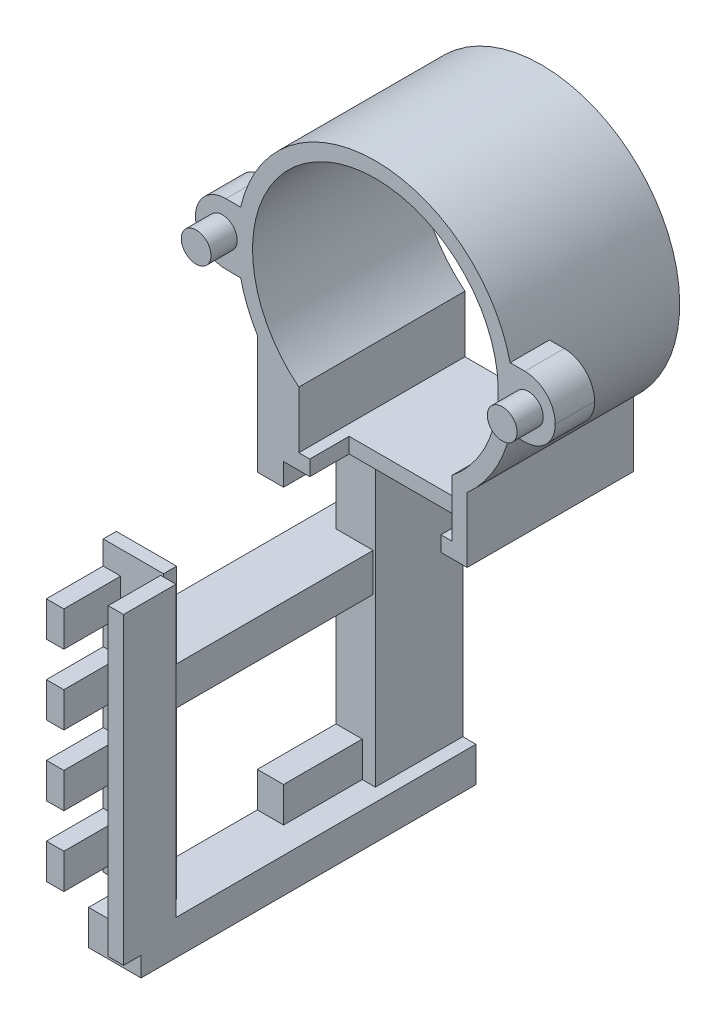
SolidWorks part; units mm, degrees
ref_plane "Plan de face" through (0, 0, 0) normal (0, 0, 1) x (1, 0, 0)
ref_plane "Plan de dessus" through (0, 0, 0) normal (0, 1, 0) x (1, 0, 0)
ref_plane "Plan de droite" through (0, 0, 0) normal (1, 0, 0) x (0, 0, -1)
sketch "Esquisse1" plane through (0, 0, 0) normal (0, 0, 1) x (1, 0, 0)
  line L0 (-10.5, -11.8064) -> (-10.5, -19.2427)
  line L2 (-8.75, -10.9927) -> (-8.75, -17.4927)
  line L3 (-8.75, -17.4927) -> (8.75, -17.4927)
  line L4 (8.75, -10.9927) -> (8.75, -17.4927)
  line L5 (-10.5, -19.2427) -> (10.5, -19.2427)
  line L6 (10.5, -11.8064) -> (10.5, -19.2427)
  arc A0 (8.75, -10.9927) -> (-8.75, -10.9927) centre (0, 0) ccw
  arc A1 (10.5, -11.8064) -> (-10.5, -11.8064) centre (0, 0) ccw
  dimension "D1" = 28.1
  dimension "D2" = 17.5
  dimension "D3" = 6.5
  dimension "D4" = 1.75
extrude "Boss.-Extru.1" add sketch "Esquisse1" along normal blind 19
sketch "Esquisse2" plane through (0, 0, 19) normal (0, 0, 1) x (1, 0, 0)
  line L0 (0, -19.2427) -> (0, 17.157) construction
  line L1 (-10.5, -19.2427) -> (10.5, -19.2427) construction
  line L2 (0, 0) -> (-25.7898, 0) construction
  line L3 (-15.4075, 3.5) -> (-17.0953, 3.5)
  line L4 (-15.4075, -3.5) -> (-17.0953, -3.5)
  line L5 (15.4075, -3.5) -> (17.0953, -3.5)
  line L6 (15.4075, 3.5) -> (17.0953, 3.5)
  circle A0 centre (-17.5, 0) radius 1.7
  arc A1 (10.5, -11.8064) -> (-10.5, -11.8064) centre (0, 0) ccw construction
  arc A2 (-17.0953, 3.5) -> (-20.5697, 0) centre (-17.0953, 0.0255) ccw
  arc A3 (-17.0953, -3.5) -> (-20.5697, 0) centre (-17.0953, -0.0255) cw
  circle A4 centre (17.5, 0) radius 1.7
  arc A5 (17.0953, -3.5) -> (20.5697, 0) centre (17.0953, -0.0255) ccw
  arc A6 (17.0953, 3.5) -> (20.5697, 0) centre (17.0953, 0.0255) cw
  arc A7 (-15.4075, -3.5) -> (-15.4075, 3.5) centre (0, 0) cw
  arc A8 (15.4075, -3.5) -> (15.4075, 3.5) centre (0, 0) ccw
  arc M1 (10.5, -11.8064) -> (-10.5, -11.8064) centre (0, 0) ccw
  dimension "D1" = 3.4
  dimension "D2" = 3.5
extrude "Boss.-Extru.8" add sketch "Esquisse2" against normal blind 4.5 separate body contours A3 L4 A0 L3 A2 M1 | A6 L6 A4 L5 A5 M1 | A0 | A4 region at (-17.5, 0, 19) region at (-15.788, 1.7707, 19) region at (17.5, 0, 19) region at (16.2514, 3.413, 19)
extrude "Boss.-Extru.9" add sketch "Esquisse2<4>" along normal blind 3 contours A0 | A4 region at (-17.5, 0, 19) region at (17.5, 0, 19)
sketch "Esquisse2<4>" plane through (0, 0, 19) normal (0, 0, 1) x (1, 0, 0) same geometry as "Esquisse2"
sketch "Esquisse5" plane through (0, -19.2427, 0) normal (0, -1, 0) x (1, 0, 0)
  line L0 (-10.5, 19) -> (10.5, 19) construction
  line L1 (-7.5, 19) -> (7.5, 19)
  line L2 (-7.5, 19) -> (-7.5, 14.5)
  line L3 (-7.5, 14.5) -> (7.5, 14.5)
  line L4 (7.5, 19) -> (7.5, 14.5)
  line L5 (0, 0) -> (0, 40.6458) construction
  line L6 (-10.5, 0) -> (10.5, 0) construction
  dimension "D1" = 4.5
  dimension "D2" = 15
  dimension "D3" = 7.5
extrude "Enlèv. mat.-Extru.1" cut sketch "Esquisse5" against normal blind 1.75
sketch "Esquisse20" plane through (-10.5, 0, 0) normal (-1, 0, 0) x (0, 0, 1)
  line L0 (19, -11.8064) -> (19, -19.2427) construction
  line L1 (0, -19.2427) -> (19, -19.2427)
  line L2 (0, -19.2427) -> (0, -15.5245)
  line L3 (0, -15.5245) -> (19, -15.5245)
  line L4 (19, -19.2427) -> (19, -15.5245)
extrude "Boss.-Extru.18" add sketch "Esquisse20" along normal blind 3
sketch "Esquisse21" plane through (0, -19.2427, 0) normal (0, -1, 0) x (1, 0, 0)
  line L0 (-13.5, 19) -> (-7.5, 19) construction
  line L1 (-13.5, 0) -> (-10.5, 0)
  line L2 (-13.5, 0) -> (-13.5, 19)
  line L3 (-13.5, 19) -> (-10.5, 19)
  line L4 (-10.5, 0) -> (-10.5, 19)
  dimension "D1" = 3
extrude "Boss.-Extru.19" add sketch "Esquisse21" along normal blind 40
sketch "Esquisse22" plane through (-10.5, 0, 0) normal (1, 0, 0) x (0, 0, -1)
  line L0 (0, -59.2427) -> (0, -19.2427) construction
  line L1 (-19, -59.2427) -> (0, -59.2427)
  line L2 (-19, -59.2427) -> (-19, -55.2427)
  line L3 (-19, -55.2427) -> (0, -55.2427)
  line L4 (0, -59.2427) -> (0, -55.2427)
  dimension "D1" = 4
extrude "Boss.-Extru.20" add sketch "Esquisse22" along normal blind 3
sketch "Esquisse23" plane through (0, 0, 19) normal (0, 0, 1) x (1, 0, 0)
  line L1 (-7.5, -55.2427) -> (-13.5, -55.2427)
  line L2 (-7.5, -55.2427) -> (-7.5, -59.2427)
  line L3 (-7.5, -59.2427) -> (-13.5, -59.2427)
  line L4 (-13.5, -55.2427) -> (-13.5, -59.2427)
extrude "Boss.-Extru.21" add sketch "Esquisse23" along normal blind 19.3
sketch "Esquisse24" plane through (0, -55.2427, 0) normal (0, 1, 0) x (1, 0, 0)
  line L1 (-7.5, -38.3) -> (-9.25, -38.3)
  line L2 (-7.5, -38.3) -> (-7.5, -34.3)
  line L3 (-7.5, -34.3) -> (-9.25, -34.3)
  line L4 (-9.25, -38.3) -> (-9.25, -34.3)
  dimension "D1" = 4
  dimension "D2" = 1.75
extrude "Boss.-Extru.22" add sketch "Esquisse24" along normal blind 33 contours L3 L4 L1 L2
sketch "Esquisse25" plane through (0, -55.2427, 0) normal (0, 1, 0) x (1, 0, 0)
  line L1 (-9.25, -38.3) -> (-11.25, -38.3)
  line L2 (-9.25, -38.3) -> (-9.25, -33.9755)
  line L3 (-9.25, -33.9755) -> (-11.25, -33.9755)
  line L4 (-11.25, -38.3) -> (-11.25, -33.9755)
  dimension "D1" = 2
extrude "Enlèv. mat.-Extru.6" cut sketch "Esquisse25" against normal blind 1.75
sketch "Esquisse26" plane through (0, -55.2427, 0) normal (0, 1, 0) x (1, 0, 0)
  line L1 (-9.25, -33.9755) -> (-12.45, -33.9755)
  line L2 (-9.25, -33.9755) -> (-9.25, -32.4755)
  line L3 (-9.25, -32.4755) -> (-12.45, -32.4755)
  line L4 (-12.45, -33.9755) -> (-12.45, -32.4755)
  point P5 (-11.25, -32.4755)
  dimension "D1" = 3.2
  dimension "D2" = 1.5
extrude "Boss.-Extru.23" add sketch "Esquisse26" along normal blind 5
sketch "Esquisse27" plane through (-12.45, 0, 0) normal (-1, 0, 0) x (0, 0, 1)
  line L1 (33.9755, -55.2427) -> (32.4755, -55.2427)
  line L2 (33.9755, -55.2427) -> (33.9755, -50.2427)
  line L3 (33.9755, -50.2427) -> (32.4755, -50.2427)
  line L4 (32.4755, -55.2427) -> (32.4755, -50.2427)
extrude "Boss.-Extru.24" add sketch "Esquisse27" along normal blind 3.7
sketch "Esquisse29" plane through (0, -15.5245, 0) normal (0, 1, 0) x (1, 0, 0)
  line L1 (-10.5, 0) -> (-13.5, 0)
  line L2 (-10.5, 0) -> (-10.5, -19)
  line L3 (-10.5, -19) -> (-13.5, -19)
  line L4 (-13.5, 0) -> (-13.5, -19)
extrude "Boss.-Extru.26" add sketch "Esquisse29" along normal up to surface (3.7182 mm away) up to face at (0, -0.6739, 14.3333)
sketch "Esquisse30" plane through (0, -19.2427, 0) normal (0, -1, 0) x (1, 0, 0)
  line L0 (-10.5, 0) -> (10.5, 0) construction
  line L1 (-9.0004, 0) -> (-10.5, 0)
  line L2 (-9.0004, 0) -> (-9.0004, 10)
  line L3 (-9.0004, 10) -> (-10.5, 10)
  line L4 (-10.5, 0) -> (-10.5, 10)
  line L5 (-10.5, 0) -> (-10.5, 19) construction
  dimension "D1" = 10
extrude "Boss.-Extru.27" add sketch "Esquisse30" along normal up to surface (36 mm away) up to face at (-10.0833, -55.2427, 22.8363)
sketch "Esquisse31" plane through (0, 0, 19) normal (0, 0, 1) x (1, 0, 0)
  line L0 (-10.5, -55.2427) -> (-10.5, -19.2427) construction
  line L1 (-10.5, -21.7913) -> (-13.5, -21.7913)
  line L2 (-10.5, -21.7913) -> (-10.5, -58.7263)
  line L3 (-10.5, -58.7263) -> (-13.5, -58.7263)
  line L4 (-13.5, -21.7913) -> (-13.5, -58.7263)
  line L5 (-13.5, -55.2427) -> (-13.5, -8.2091) construction
extrude "Enlèv. mat.-Extru.7" cut sketch "Esquisse31" against normal up to surface (9 mm away) up to face at (-9.7502, -37.2427, 10)
sketch "Esquisse32" plane through (0, -58.7263, 0) normal (0, 1, 0) x (1, 0, 0)
  line L0 (-13.5, -10) -> (-13.5, -19) construction
  line L1 (-10.5, -10) -> (-13.5, -10)
  line L2 (-10.5, -10) -> (-10.5, -19)
  line L3 (-10.5, -19) -> (-13.5, -19)
  line L4 (-13.5, -10) -> (-13.5, -19)
extrude "Boss.-Extru.28" add sketch "Esquisse32" along normal blind 7.5
sketch "Esquisse33" plane through (0, -50.2427, 0) normal (0, 1, 0) x (1, 0, 0)
  line L1 (-16.15, -33.9755) -> (-9.25, -33.9755)
  line L2 (-16.15, -33.9755) -> (-16.15, -32.4755)
  line L3 (-16.15, -32.4755) -> (-9.25, -32.4755)
  line L4 (-9.25, -33.9755) -> (-9.25, -32.4755)
  point P6 (-14.95, -33.9755)
  point P7 (-14.95, -33.9755)
extrude "Boss.-Extru.29" add sketch "Esquisse33" along normal blind 28
sketch "Esquisse34" plane through (0, 0, 32.4755) normal (0, 0, -1) x (-1, 0, 0)
  line L0 (16.15, -22.2427) -> (16.15, -55.2427) construction
  line L1 (16.15, -31.9118) -> (9.25, -31.9118)
  line L2 (16.15, -31.9118) -> (16.15, -36.2752)
  line L3 (16.15, -36.2752) -> (9.25, -36.2752)
  line L4 (9.25, -31.9118) -> (9.25, -36.2752)
  line L5 (9.25, -22.2427) -> (9.25, -55.2427) construction
extrude "Boss.-Extru.30" add sketch "Esquisse34" along normal up to surface (22.4755 mm away) up to face at (-10.8751, -36.8758, 10)
sketch "Esquisse35" plane through (0, 0, 10) normal (0, 0, -1) x (-1, 0, 0)
  line L0 (13.5, -8.2091) -> (13.5, -59.2427) construction
  line L1 (16.15, -31.9118) -> (13.5, -31.9118)
  line L2 (16.15, -31.9118) -> (16.15, -36.2752)
  line L3 (16.15, -36.2752) -> (13.5, -36.2752)
  line L4 (13.5, -31.9118) -> (13.5, -36.2752)
  line L5 (9.25, -36.2752) -> (16.15, -36.2752) construction
extrude "Boss.-Extru.31" add sketch "Esquisse35" along normal up to surface (10 mm away) up to face at (-4.3949, -32.7298, 0)
sketch "Esquisse36" plane through (0, 0, 33.9755) normal (0, 0, 1) x (1, 0, 0)
  line L0 (-16.15, -55.2427) -> (-16.15, -22.2427) construction
  line L1 (-16.15, -24.9257) -> (-14.15, -24.9257)
  line L2 (-16.15, -24.9257) -> (-16.15, -28.9257)
  line L3 (-16.15, -28.9257) -> (-14.15, -28.9257)
  line L4 (-14.15, -24.9257) -> (-14.15, -28.9257)
  line L5 (-14.15, -32.9257) -> (-14.15, -36.9257)
  line L6 (-16.15, -32.9257) -> (-14.15, -32.9257)
  line L7 (-16.15, -32.9257) -> (-16.15, -36.9257)
  line L8 (-16.15, -36.9257) -> (-14.15, -36.9257)
  line L9 (-14.15, -40.9257) -> (-14.15, -44.9257)
  line L10 (-16.15, -40.9257) -> (-14.15, -40.9257)
  line L11 (-16.15, -40.9257) -> (-16.15, -44.9257)
  line L12 (-16.15, -44.9257) -> (-14.15, -44.9257)
  line L13 (-14.15, -48.9257) -> (-14.15, -52.9257)
  line L14 (-16.15, -48.9257) -> (-14.15, -48.9257)
  line L15 (-16.15, -48.9257) -> (-16.15, -52.9257)
  line L16 (-16.15, -52.9257) -> (-14.15, -52.9257)
  point P6 (-12.95, -27.7843)
  point P7 (-12.95, -28.2348)
  point P20 (-12.95, -25.7555)
  point P21 (-12.95, -23.9282)
  point P22 (-12.95, -24.9257)
  dimension "D1" = 4
  dimension "D2" = 2
  dimension "D3" = 4
extrude "Boss.-Extru.32" add sketch "Esquisse36" along normal blind 6.5
sketch "Esquisse37" plane through (0, 0, 38.3) normal (0, 0, 1) x (1, 0, 0)
  line L1 (-7.5, -22.2427) -> (-9.25, -22.2427)
  line L2 (-7.5, -22.2427) -> (-7.5, -56.9927)
  line L3 (-7.5, -56.9927) -> (-9.25, -56.9927)
  line L4 (-9.25, -22.2427) -> (-9.25, -56.9927)
  point P5 (-9.25, -56.9927)
extrude "Boss.-Extru.33" add sketch "Esquisse37" along normal blind 2
